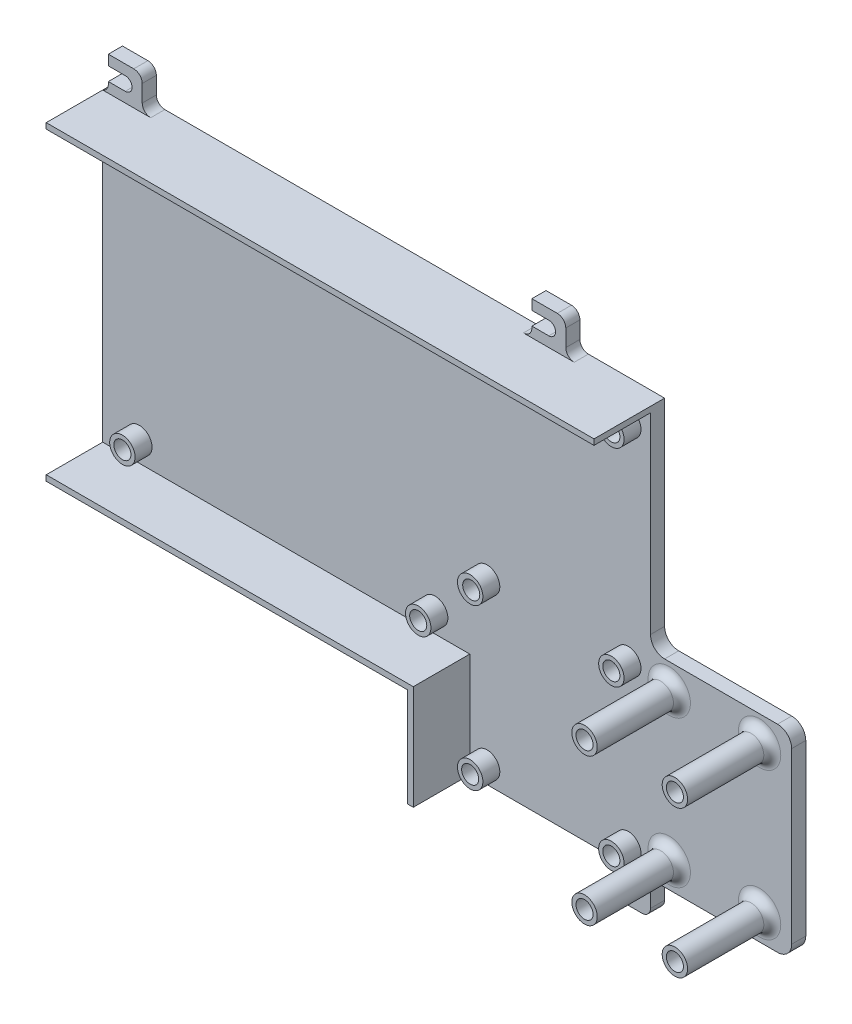
SolidWorks part; units mm, degrees
material "ABS"
ref_plane "X-Y Datum" through (0, 0, 0) normal (0, 0, 1) x (1, 0, 0)
ref_plane "X-Z Datum" through (0, 0, 0) normal (0, 1, 0) x (1, 0, 0)
ref_plane "Y-Z Datum" through (0, 0, 0) normal (1, 0, 0) x (0, 0, -1)
sketch "Sketch1" plane through (0, 0, 0) normal (0, 0, 1) x (1, 0, 0)
  line L1 (-167.3248, 270.3744) -> (-39.3248, 270.3744)
  line L2 (-167.3248, 270.3744) -> (-167.3248, 160.3744)
  line L3 (-167.3248, 160.3744) -> (-39.3248, 160.3744)
  line L4 (-39.3248, 270.3744) -> (-39.3248, 160.3744)
  line L5 (-39.3248, 270.3744) -> (26.6752, 270.3744)
  line L6 (-39.3248, 270.3744) -> (-39.3248, 125.3744)
  line L7 (-39.3248, 125.3744) -> (26.6752, 125.3744)
  line L8 (26.6752, 270.3744) -> (26.6752, 125.3744)
  line L9 (26.6752, 125.3744) -> (76.6752, 125.3744)
  line L10 (26.6752, 125.3744) -> (26.6752, 195.3744)
  line L11 (26.6752, 195.3744) -> (76.6752, 195.3744)
  line L12 (76.6752, 125.3744) -> (76.6752, 195.3744)
  dimension "D1" = 110
  dimension "D2" = 128
  dimension "D3" = 66
  dimension "D4" = 145
  dimension "D5" = 50
  dimension "D6" = 70
extrude "Boss-Extrude1" add sketch "Sketch1" along normal blind 5 contours L4 L1 L2 L3 | L8 L5 L4 L6 L7 | L9 L12 L11 L8 region at (-103.3248, 215.3744, 0) region at (-6.3248, 197.8744, 0) region at (51.6752, 160.3744, 0)
sketch "Sketch3" plane through (0, 0, 5) normal (0, 0, 1) x (1, 0, 0)
  line L0 (26.6752, 270.3744) -> (26.6752, 195.3744) construction
  line L1 (-167.3248, 270.3744) -> (26.6752, 270.3744)
  line L2 (-167.3248, 270.3744) -> (-167.3248, 268.3744)
  line L3 (-167.3248, 268.3744) -> (26.6752, 268.3744)
  line L4 (26.6752, 270.3744) -> (26.6752, 268.3744)
  line L6 (-167.3248, 160.3744) -> (-39.3248, 160.3744)
  line L7 (-167.3248, 160.3744) -> (-167.3248, 162.3744)
  line L8 (-167.3248, 162.3744) -> (-39.3248, 162.3744)
  line L9 (-39.3248, 160.3744) -> (-39.3248, 162.3744)
  line L10 (-39.3248, 125.3744) -> (-37.3248, 125.3744)
  line L11 (-39.3248, 125.3744) -> (-39.3248, 162.3744)
  line L12 (-39.3248, 162.3744) -> (-37.3248, 162.3744)
  line L13 (-37.3248, 125.3744) -> (-37.3248, 162.3744)
  line M14 (-167.3248, 160.3744) -> (-39.3248, 160.3744)
  line M15 (-39.3248, 160.3744) -> (-39.3248, 125.3744)
  line M16 (-39.3248, 125.3744) -> (76.6752, 125.3744)
  line M19 (26.6752, 195.3744) -> (26.6752, 270.3744)
  line M20 (26.6752, 270.3744) -> (-167.3248, 270.3744)
  line M21 (-167.3248, 270.3744) -> (-167.3248, 160.3744)
  dimension "D1" = 2
  dimension "D2" = 2
  dimension "D3" = 2
extrude "Boss-Extrude3" add sketch "Sketch3" along normal blind 20 contours L13 L12 L9 M16 M15 | L9 L8 M14 M21 | L3 M21 M19 M20 region at (-103.3248, 161.3744, 5) region at (-70.3248, 269.3744, 5) region at (-38.3248, 143.8744, 5)
sketch "Sketch6" plane through (0, 0, 0) normal (0, 0, -1) x (-1, 0, 0)
  line L0 (167.3248, 160.3744) -> (39.3248, 160.3744) construction
  line L1 (102.3248, 160.3744) -> (90.3248, 160.3744)
  line L2 (102.3248, 160.3744) -> (102.3248, 148.3744)
  line L3 (102.3248, 148.3744) -> (90.3248, 148.3744)
  line L4 (90.3248, 160.3744) -> (90.3248, 148.3744)
  line L5 (-26.6752, 270.3744) -> (167.3248, 270.3744) construction
  line L6 (165.3248, 270.3744) -> (153.3248, 270.3744)
  line L7 (165.3248, 270.3744) -> (165.3248, 282.3744)
  line L8 (165.3248, 282.3744) -> (153.3248, 282.3744)
  line L9 (153.3248, 270.3744) -> (153.3248, 282.3744)
  line L10 (37.3248, 125.3744) -> (-76.6752, 125.3744) construction
  line L11 (-14.6752, 125.3744) -> (-26.6752, 125.3744)
  line L12 (-14.6752, 125.3744) -> (-14.6752, 113.3744)
  line L13 (-14.6752, 113.3744) -> (-26.6752, 113.3744)
  line L14 (-26.6752, 125.3744) -> (-26.6752, 113.3744)
  line L15 (96.3248, 160.3744) -> (96.3248, 148.3744) construction
  line L16 (15.3248, 270.3744) -> (3.3248, 270.3744)
  line L17 (15.3248, 270.3744) -> (15.3248, 282.3744)
  line L18 (15.3248, 282.3744) -> (3.3248, 282.3744)
  line L19 (3.3248, 270.3744) -> (3.3248, 282.3744)
  line L20 (167.3248, 162.3744) -> (167.3248, 160.3744) construction
  line L21 (159.3248, 282.3744) -> (159.3248, 270.3744) construction
  line L22 (9.3248, 282.3744) -> (9.3248, 270.3744) construction
  line L23 (-20.6752, 125.3744) -> (-20.6752, 113.3744) construction
  line L24 (167.3248, 268.3744) -> (167.3248, 162.3744) construction
  line L27 (-26.6752, 268.3744) -> (-26.6752, 195.3744) construction
  line L28 (-76.6752, 125.3744) -> (-76.6752, 195.3744) construction
  circle A0 centre (96.3248, 154.3744) radius 2 construction
  circle A1 centre (-20.6752, 119.3744) radius 2 construction
  circle A2 centre (9.3248, 276.3744) radius 2 construction
  circle A3 centre (159.3248, 276.3744) radius 2 construction
  dimension "D1" = 4
  dimension "D2" = 12
  dimension "D3" = 12
  dimension "D4" = 65
  dimension "D5" = 2
  dimension "D6" = 30
  dimension "D7" = 50
extrude "Boss-Extrude5" add sketch "Sketch6" against normal blind 5
hole_wizard "M4 Clearance Hole1" positions "Sketch9" profile "Sketch8" hole size "M4" standard "ANSI Metric" end condition through all
sketch "Sketch9" plane through (0, 0, 5) normal (0, 0, 1) x (1, 0, 0)
  line L0 (-96.3248, 160.3744) -> (-96.3248, 148.3744) construction
  point P0 (-96.3248, 154.3744)
  point P4 (-159.3248, 276.3744)
  point P7 (-9.3248, 276.3744)
  point P10 (20.6752, 119.3744)
sketch "Sketch8" plane through (-96.3248, 154.3744, 5) normal (1, 0, 0) x (0, -1, 0)
  line L0 (0, 0) -> (0, 5)
  line L1 (0, 5) -> (2.4, 5)
  line L2 (2.4, 5) -> (2.4, 0)
  line L5 (2.4, 0) -> (0, 0)
  line L11 (0, -6.35) -> (0, 107.95) construction
  dimension "Thru Hole Dia." = 4.8
  dimension "Thru Hole Depth" = 5
sketch "Sketch10" plane through (0, 0, 5) normal (0, 0, 1) x (1, 0, 0)
  line L0 (-159.3248, 278.7744) -> (-165.3248, 278.7744)
  line L1 (-159.3248, 282.3744) -> (-159.3248, 270.3744) construction
  line L2 (-165.3248, 270.3744) -> (-165.3248, 282.3744) construction
  line L3 (-159.3248, 273.9744) -> (-165.3248, 273.9744)
  line L4 (-96.3248, 156.7744) -> (-102.3248, 156.7744)
  line L5 (-96.3248, 160.3744) -> (-96.3248, 148.3744) construction
  line L6 (-102.3248, 160.3744) -> (-102.3248, 148.3744) construction
  line L7 (-96.3248, 151.9744) -> (-102.3248, 151.9744)
  line L8 (20.6752, 121.7744) -> (14.6752, 121.7744)
  line L9 (20.6752, 125.3744) -> (20.6752, 113.3744) construction
  line L10 (14.6752, 125.3744) -> (14.6752, 113.3744) construction
  line L11 (20.6752, 116.9744) -> (14.6752, 116.9744)
  line L12 (-9.3248, 278.7744) -> (-15.3248, 278.7744)
  line L13 (-9.3248, 282.3744) -> (-9.3248, 270.3744) construction
  line L14 (-15.3248, 270.3744) -> (-15.3248, 282.3744) construction
  line L15 (-9.3248, 273.9744) -> (-15.3248, 273.9744)
  line L20 (-102.3248, 160.3744) -> (-102.3248, 148.3744)
  line L21 (-102.3248, 148.3744) -> (-90.3248, 148.3744)
  line L22 (-90.3248, 148.3744) -> (-90.3248, 160.3744)
  line L23 (-90.3248, 160.3744) -> (-102.3248, 160.3744)
  line L24 (-102.3248, 160.3744) -> (-102.3248, 148.3744)
  line L25 (-102.3248, 148.3744) -> (-90.3248, 148.3744)
  line L26 (-90.3248, 148.3744) -> (-90.3248, 160.3744)
  line L27 (-90.3248, 160.3744) -> (-102.3248, 160.3744)
  line L28 (-15.3248, 282.3744) -> (-15.3248, 270.3744)
  line L29 (-15.3248, 270.3744) -> (-3.3248, 270.3744)
  line L30 (76.6752, 125.3744) -> (76.6752, 195.3744)
  line L32 (76.6752, 195.3744) -> (26.6752, 195.3744)
  line L33 (26.6752, 195.3744) -> (26.6752, 268.3744)
  line L34 (26.6752, 268.3744) -> (-167.3248, 268.3744)
  line L35 (-167.3248, 268.3744) -> (-167.3248, 162.3744)
  line L36 (-167.3248, 162.3744) -> (-37.3248, 162.3744)
  line L37 (-37.3248, 162.3744) -> (-37.3248, 125.3744)
  line L38 (-37.3248, 125.3744) -> (14.6752, 125.3744)
  line L39 (14.6752, 125.3744) -> (14.6752, 113.3744)
  line L40 (14.6752, 113.3744) -> (26.6752, 113.3744)
  line L41 (26.6752, 113.3744) -> (26.6752, 125.3744)
  line L44 (76.6752, 125.3744) -> (76.6752, 195.3744)
  line L46 (76.6752, 195.3744) -> (26.6752, 195.3744)
  line L47 (26.6752, 195.3744) -> (26.6752, 268.3744)
  line L48 (26.6752, 268.3744) -> (-167.3248, 268.3744)
  line L49 (-167.3248, 268.3744) -> (-167.3248, 162.3744)
  line L50 (-167.3248, 162.3744) -> (-37.3248, 162.3744)
  line L51 (-37.3248, 162.3744) -> (-37.3248, 125.3744)
  line L52 (-37.3248, 125.3744) -> (14.6752, 125.3744)
  line L53 (14.6752, 125.3744) -> (14.6752, 113.3744)
  line L54 (14.6752, 113.3744) -> (26.6752, 113.3744)
  line L55 (26.6752, 113.3744) -> (26.6752, 125.3744)
  line L58 (-3.3248, 270.3744) -> (-3.3248, 282.3744)
  line L59 (-3.3248, 282.3744) -> (-15.3248, 282.3744)
  line L60 (-15.3248, 282.3744) -> (-15.3248, 270.3744)
  line L61 (-15.3248, 270.3744) -> (-3.3248, 270.3744)
  line L62 (-3.3248, 270.3744) -> (-3.3248, 282.3744)
  line L63 (-3.3248, 282.3744) -> (-15.3248, 282.3744)
  line L64 (-165.3248, 282.3744) -> (-165.3248, 270.3744)
  line L65 (-165.3248, 270.3744) -> (-153.3248, 270.3744)
  line L66 (-153.3248, 270.3744) -> (-153.3248, 282.3744)
  line L67 (-153.3248, 282.3744) -> (-165.3248, 282.3744)
  line L68 (-165.3248, 282.3744) -> (-165.3248, 270.3744)
  line L69 (-165.3248, 270.3744) -> (-153.3248, 270.3744)
  line L70 (-153.3248, 270.3744) -> (-153.3248, 282.3744)
  line L71 (-153.3248, 282.3744) -> (-165.3248, 282.3744)
  line L80 (26.6752, 125.3744) -> (76.6752, 125.3744)
  line L81 (26.6752, 125.3744) -> (76.6752, 125.3744)
  circle A0 centre (-159.3248, 276.3744) radius 2.4 construction
  circle A1 centre (-96.3248, 154.3744) radius 2.4 construction
  circle A2 centre (20.6752, 119.3744) radius 2.4 construction
  circle A3 centre (-9.3248, 276.3744) radius 2.4 construction
  circle A4 centre (-159.3248, 276.3744) radius 2.4
  circle A5 centre (-9.3248, 276.3744) radius 2.4
  circle A10 centre (20.6752, 119.3744) radius 2.4
  circle A11 centre (-96.3248, 154.3744) radius 2.4
  circle M29 centre (-96.3248, 154.3744) radius 2.4
  line M30 (-102.3248, 160.3744) -> (-102.3248, 148.3744)
  dimension "D1" = 0
  dimension "D2" = 0
  dimension "D3" = 0
  dimension "D4" = 0
extrude "Cut-Extrude1" cut sketch "Sketch10" against normal through all contours L7 L4 M29 M30 | A4 L0 L68 L3 | A5 L12 L60 L15 | A10 L8 L53 L11 region at (-163.2324, 276.3744, 5) region at (-100.2324, 154.3744, 5) region at (16.7676, 119.3744, 5) region at (-13.2324, 276.3744, 5)
fillet "Fillet2" radius 3 12 edges at (-153.3248, 282.3744, 2.5) (-153.3248, 270.3744, 2.5) (-165.3248, 270.3744, 2.5) (-15.3248, 270.3744, 2.5) (-3.3248, 270.3744, 2.5) (-3.3248, 282.3744, 2.5) (-90.3248, 148.3744, 2.5) (26.6752, 113.3744, 2.5) (26.6752, 125.3744, 2.5) (14.6752, 125.3744, 2.5) (-102.3248, 160.3744, 2.5) (-90.3248, 160.3744, 2.5)
fillet "Fillet3" radius 5 3 edges at (26.6752, 195.3744, 2.5) (76.6752, 195.3744, 2.5) (76.6752, 125.3744, 2.5)
sketch "Sketch15" plane through (0, 0, 5) normal (0, 0, 1) x (1, 0, 0)
  circle A0 centre (-49.5798, 262.4914) radius 3.025
  circle A1 centre (-31.1818, 261.5554) radius 3.025
  circle A2 centre (18.8182, 261.5554) radius 3.025
  circle A3 centre (-154.3548, 169.5274) radius 3.025
  circle A4 centre (-49.5798, 169.5274) radius 3.025
  circle A5 centre (-30.8078, 188.3054) radius 3.025
  circle A6 centre (-31.1818, 131.5554) radius 3.025
  circle A7 centre (18.8182, 131.5554) radius 3.025
  circle A8 centre (18.8182, 188.3054) radius 3.025
  circle A20 centre (-154.3548, 262.4914) radius 3.025
  circle A21 centre (-154.3548, 169.5274) radius 4.5
  circle A22 centre (-49.5798, 262.4914) radius 4.5
  circle A23 centre (-49.5798, 169.5274) radius 4.5
  circle A24 centre (-31.1818, 131.5554) radius 4.5
  circle A25 centre (-31.1818, 188.3054) radius 4.5
  circle A26 centre (18.8182, 188.3054) radius 4.5
  circle A27 centre (18.8182, 131.5554) radius 4.5
  circle A28 centre (-31.1818, 261.5554) radius 4.5
  circle A29 centre (18.8182, 261.5554) radius 4.5
  circle A30 centre (-154.3548, 262.4914) radius 4.5
  dimension "D1" = 6.05
  dimension "D2" = 9
extrude "Boss-Extrude6" add sketch "Sketch15" along normal blind 6
sketch "Sketch16" plane through (0, 0, 5) normal (0, 0, 1) x (1, 0, 0)
  circle A0 centre (33.3182, 134.3744) radius 2.4 construction
  circle A1 centre (65.3182, 134.3744) radius 2.4 construction
  circle A2 centre (65.3182, 186.3744) radius 2.4 construction
  circle A3 centre (33.3182, 186.3744) radius 2.4 construction
  circle A4 centre (33.3182, 134.3744) radius 2.4 construction
  circle A5 centre (65.3182, 134.3744) radius 2.4 construction
  circle A6 centre (65.3182, 186.3744) radius 2.4 construction
  circle A7 centre (33.3182, 186.3744) radius 2.4 construction
  circle A8 centre (33.3182, 134.3744) radius 3.025
  circle A9 centre (65.3182, 134.3744) radius 3.025
  circle A10 centre (33.3182, 186.3744) radius 3.025
  circle A11 centre (65.3182, 186.3744) radius 3.025
  circle A12 centre (33.3182, 134.3744) radius 4.5
  circle A13 centre (65.3182, 134.3744) radius 4.5
  circle A14 centre (65.3182, 186.3744) radius 4.5
  circle A15 centre (33.3182, 186.3744) radius 4.5
  dimension "D1" = 6.05
  dimension "D2" = 9
extrude "Boss-Extrude7" add sketch "Sketch16" along normal blind 30
fillet "Fillet4" radius 3 4 edges at (37.8182, 186.3744, 5) (69.8182, 186.3744, 5) (69.8182, 134.3744, 5) (37.8182, 134.3744, 5)
equation "\"16mmm\"=20"
